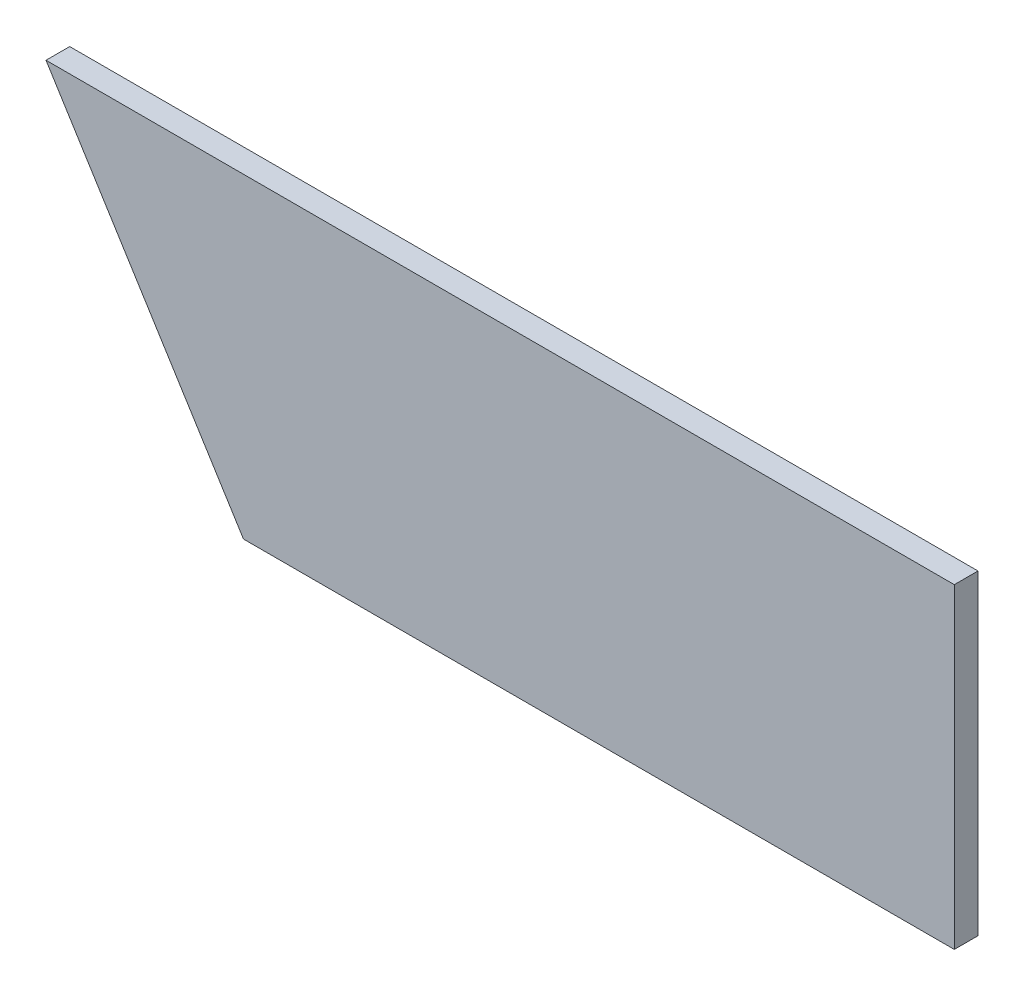
SolidWorks part; units mm, degrees
ref_plane "Plan de face" through (0, 0, 0) normal (0, 0, 1) x (1, 0, 0)
ref_plane "Plan de dessus" through (0, 0, 0) normal (0, 1, 0) x (1, 0, 0)
ref_plane "Plan de droite" through (0, 0, 0) normal (1, 0, 0) x (0, 0, -1)
sketch "Esquisse1" plane through (0, 0, 0) normal (0, 0, 1) x (1, 0, 0)
  line L0 (115, 0) -> (25, 0) construction
  line L1 (25, 0) -> (115, 0)
  line L3 (0, 40) -> (115, 40)
  line L4 (115, 0) -> (115, 40)
  line L5 (0, 40) -> (25, 0)
  dimension "D1" = 115
  dimension "D3" = 90
base flange "Tôle de base pliée1" sketch "Esquisse1" thickness 3 reverse thickness direction no parameters "D1"=0.7366
sketch "Lignes de pliage1" [suppressed] plane through (0, 0, 0) normal (0, 1, 0) x (1, 0, 0)
sketch "Cube de visualisation1" [suppressed] plane through (0, 0, 0) normal (0, 1, 0) x (1, 0, 0)
sheet metal parameters "Tôlerie1" thickness 3 parameters "D1"=0.7366
flat pattern "Etat déplié1" [suppressed]
sketch "Lignes de pliage2" plane through (0, 0, 0) normal (0, 1, 0) x (1, 0, 0)
sketch3d "Cube de visualisation2" [suppressed]
  line L0 (0, 0, 0) -> (-115, 0, 0) construction
  line L1 (0, 40, 0) -> (-115, 40, 0) construction
  line L2 (0, 0, 0) -> (0, 40, 0) construction
  line L3 (-115, 0, 0) -> (-115, 40, 0) construction
